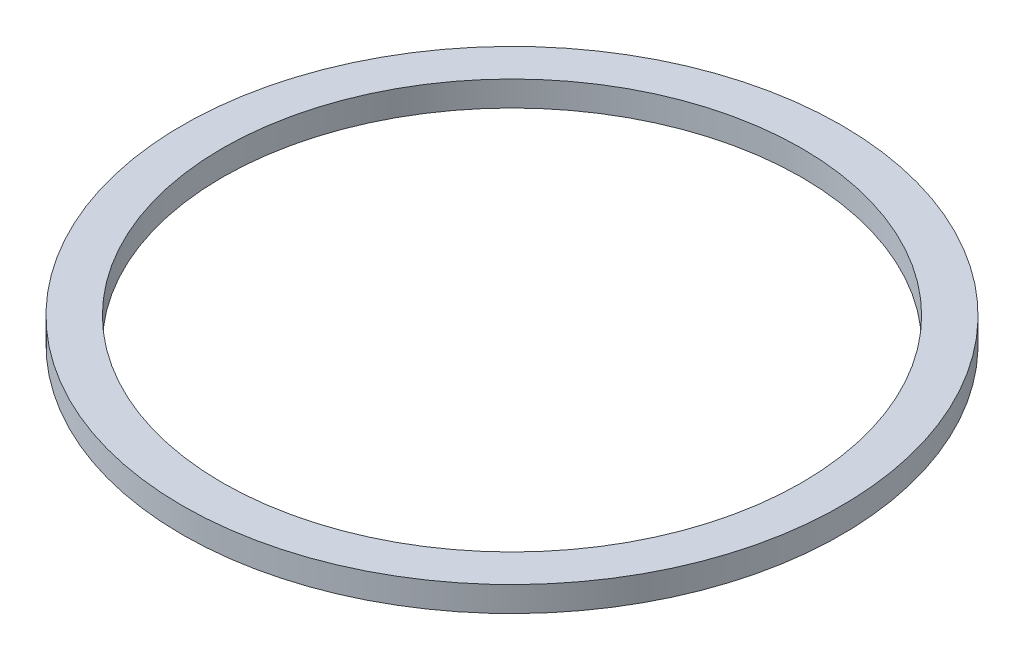
SolidWorks part; units mm, degrees
ref_plane "Front Plane" through (0, 0, 0) normal (0, 0, 1) x (1, 0, 0)
ref_plane "Top Plane" through (0, 0, 0) normal (0, 1, 0) x (1, 0, 0)
ref_plane "Right Plane" through (0, 0, 0) normal (1, 0, 0) x (0, 0, -1)
sketch "Sketch1" plane through (0, 0, 0) normal (0, 1, 0) x (1, 0, 0)
  circle A0 centre (0, 0) radius 111.5
  circle A1 centre (0, 0) radius 98
  dimension "D1" = 223
  dimension "D2" = 196
extrude "Boss-Extrude1" add sketch "Sketch1" along normal blind 8.5
